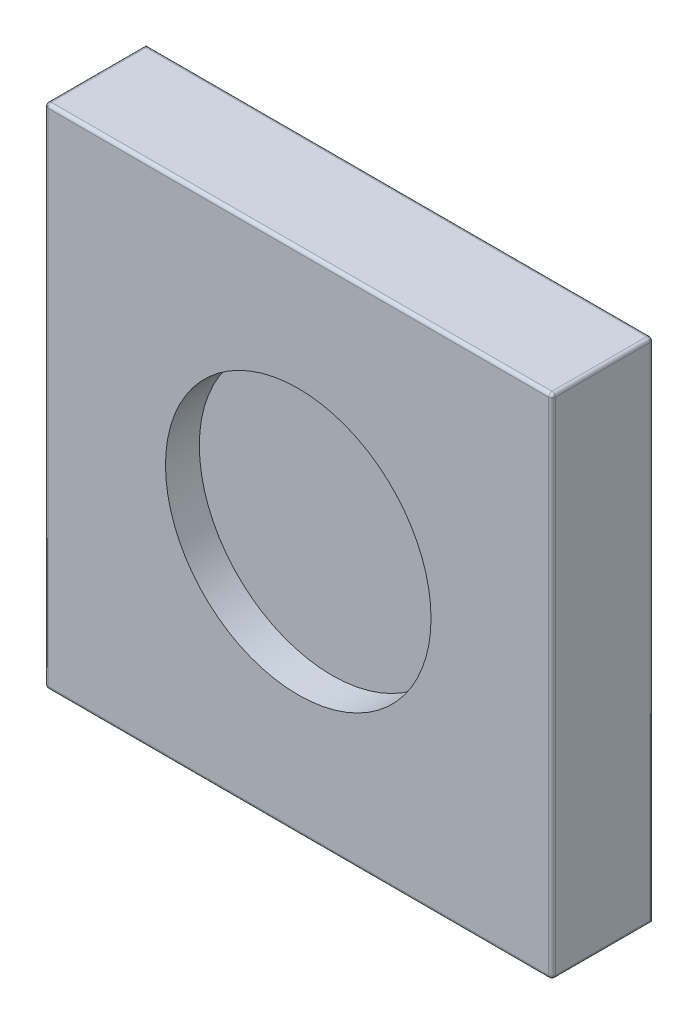
SolidWorks part; units mm, degrees
material "PLA"
ref_plane "Front Plane" through (0, 0, 0) normal (0, 0, 1) x (1, 0, 0)
ref_plane "Top Plane" through (0, 0, 0) normal (0, 1, 0) x (1, 0, 0)
ref_plane "Right Plane" through (0, 0, 0) normal (1, 0, 0) x (0, 0, -1)
sketch "Sketch1" plane through (0, 0, 0) normal (0, 0, 1) x (1, 0, 0)
  line L1 (-75, -75) -> (75, -75)
  line L2 (-75, -75) -> (-75, 75)
  line L3 (-75, 75) -> (75, 75)
  line L4 (75, -75) -> (75, 75)
  line L5 (-75, -75) -> (75, 75) construction
  line L6 (-75, 75) -> (75, -75) construction
  point P0 (0, 0)
  dimension "D1" = 150
  dimension "D2" = 150
extrude "Boss-Extrude1" add sketch "Sketch1" against normal blind 30 contours L2 L3 L4 L1
sketch "Sketch2" plane through (0, 0, 0) normal (0, 0, 1) x (1, 0, 0)
  circle A0 centre (0, 0) radius 39.25
  point P3 (0, 0)
  dimension "D1" = 78.5
fillet "Fillet1" radius 1 10 edges at (75, -75, -15) (-75, -75, -15) (-75, 75, -15) (75, 0, -30) (0, 75, -30) (75, 75, -15) (0, -75, 0) (-75, 0, 0) (75, 0, 0) (0, 75, 0)
sketch "Sketch7" plane through (0, 0, 0) normal (0, 1, 0) x (1, 0, 0)
  line L1 (-39.7685, 40.3246) -> (-29.7685, 40.3246)
  line L2 (-39.7685, 40.3246) -> (-39.7685, 30.3246)
  line L3 (-39.7685, 30.3246) -> (-29.7685, 30.3246)
  line L4 (-29.7685, 40.3246) -> (-29.7685, 30.3246)
  dimension "D1" = 10
  dimension "D2" = 10
ref_axis "Axis2" through (0, 0, 0) along (0, 0, -1)
extrude "Cut-Extrude4" cut sketch "Sketch2" against normal blind 10 contours A0
